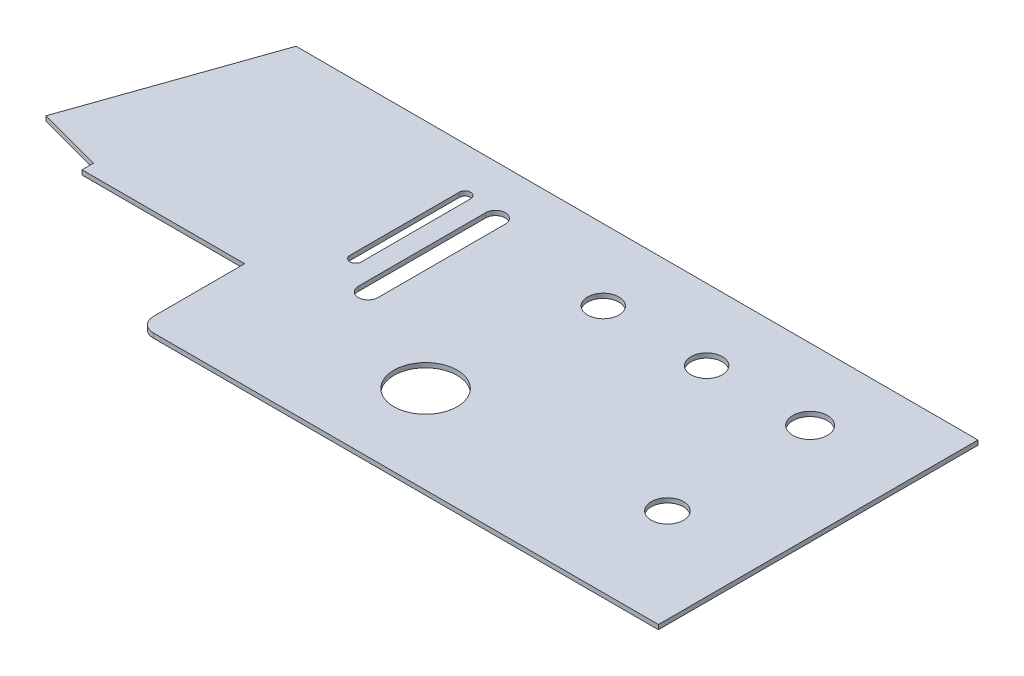
SolidWorks part; units mm, degrees
ref_plane "Front Plane" through (0, 0, 0) normal (0, 0, 1) x (1, 0, 0)
ref_plane "Top Plane" through (0, 0, 0) normal (0, 1, 0) x (1, 0, 0)
ref_plane "Right Plane" through (0, 0, 0) normal (1, 0, 0) x (0, 0, -1)
sketch "Sketch1" plane through (0, 0, 0) normal (0, 1, 0) x (1, 0, 0)
  line L0 (-101.3722, -12.5155) -> (-44.3722, -12.5155) construction
  line L1 (-44.3722, -53.5155) -> (137.6278, -53.5155) construction
  line L2 (-101.3722, -12.5155) -> (-101.3722, 58.4845) construction
  line L3 (-101.3722, 58.4845) -> (137.6278, 58.4845) construction
  line L4 (137.6278, -53.5155) -> (137.6278, 58.4845) construction
  line L5 (-44.3722, -12.5155) -> (-44.3722, -53.5155) construction
  line L6 (-26.4722, 42.7845) -> (-26.4722, 4.4845) construction
  line L7 (-23.4722, 42.7845) -> (-23.4722, 4.4845) construction
  line L8 (-29.4722, 42.7845) -> (-29.4722, 4.4845) construction
  line L9 (-14.1722, 41.1845) -> (-14.1722, -3.4155) construction
  line L10 (-9.5722, 41.1845) -> (-9.5722, -3.4155) construction
  line L11 (-18.7722, 41.1845) -> (-18.7722, -3.4155) construction
  line L12 (-26.4722, 45.7845) -> (-43.4588, 45.7845) construction
  line L13 (-26.4722, 1.4845) -> (-43.4588, 1.4845) construction
  line L14 (-14.1722, -8.0155) -> (-3.3024, -8.0155) construction
  line L15 (-14.1722, 45.7845) -> (0, 45.7845) construction
  line L16 (31.286, 33.4845) -> (122.5273, 33.4845) construction
  arc A0 (-23.4722, 42.7845) -> (-29.4722, 42.7845) centre (-26.4722, 42.7845) ccw construction
  arc A1 (-29.4722, 4.4845) -> (-23.4722, 4.4845) centre (-26.4722, 4.4845) ccw construction
  arc A2 (-9.5722, 41.1845) -> (-18.7722, 41.1845) centre (-14.1722, 41.1845) ccw construction
  arc A3 (-18.7722, -3.4155) -> (-9.5722, -3.4155) centre (-14.1722, -3.4155) ccw construction
  circle A7 centre (25.1778, -22.6655) radius 11.15 construction
  circle A8 centre (104.7278, -17.4655) radius 5.95 construction
  circle A9 centre (31.286, 33.4845) radius 6.25 construction
  circle A10 centre (67.536, 33.4845) radius 6.25 construction
  circle A11 centre (103.786, 33.4845) radius 6.25 construction
  point P0 (0, 0)
  point P10 (-26.4722, 23.6345)
  point P15 (-14.1722, 18.8845)
  point P24 (0, 0)
  dimension "D5" = 3
  dimension "D6" = 4.6
  dimension "D7" = 44.3
  dimension "D9" = 12.5
  dimension "D10" = 22.3
  dimension "D11" = 11.9
  dimension "D14" = 149.1
  dimension "D16" = 12.7
  dimension "D19" = 81.15
  dimension "D1" = 239
  dimension "D2" = 182
  dimension "D3" = 74.9
  dimension "D4" = 87.2
  dimension "D8" = 53.8
  dimension "D12" = 112
  dimension "D13" = 69.55
  dimension "D15" = 12.7
  dimension "D17" = 25
  dimension "D20" = 75.95
  dimension "D21" = 71
  dimension "D22" = 41
  dimension "D18" = 3
sketch "Sketch2" plane through (0, 0, 0) normal (0, 1, 0) x (1, 0, 0)
  line L1 (-101.3722, 58.4845) -> (137.6278, 58.4845)
  line L3 (-39.3722, -53.5155) -> (137.6278, -53.5155)
  line L4 (137.6278, 58.4845) -> (137.6278, -53.5155)
  line L5 (-44.3722, -16.5155) -> (-44.3722, -48.5155)
  line L6 (-26.4722, 4.4845) -> (-26.4722, 42.7845) construction
  line L7 (-28.4722, 4.4845) -> (-28.4722, 42.7845)
  line L8 (-24.4722, 4.4845) -> (-24.4722, 42.7845)
  line L9 (-14.1722, 41.1845) -> (-14.1722, -3.4155) construction
  line L10 (-10.7222, 41.1845) -> (-10.7222, -3.4155)
  line L11 (-17.6222, 41.1845) -> (-17.6222, -3.4155)
  line L12 (-101.3722, -12.5155) -> (-101.3722, -16.5155)
  line L13 (-101.3722, -16.5155) -> (-44.8722, -16.5155)
  line L15 (-101.3722, -12.5155) -> (-124.0715, -6.4333)
  line L16 (-124.0715, -6.4333) -> (-101.3722, 58.4845)
  line L17 (-44.8722, -16.5155) -> (-44.3722, -16.5155)
  arc A0 (-28.4722, 4.4845) -> (-24.4722, 4.4845) centre (-26.4722, 4.4845) ccw
  arc A1 (-24.4722, 42.7845) -> (-28.4722, 42.7845) centre (-26.4722, 42.7845) ccw
  arc A2 (-10.7222, 41.1845) -> (-17.6222, 41.1845) centre (-14.1722, 41.1845) ccw
  arc A3 (-17.6222, -3.4155) -> (-10.7222, -3.4155) centre (-14.1722, -3.4155) ccw
  circle A4 centre (31.286, 33.4845) radius 5.5
  circle A5 centre (67.536, 33.4845) radius 5.5
  circle A6 centre (103.786, 33.4845) radius 6.05
  circle A7 centre (25.1778, -22.6655) radius 11.1
  circle A8 centre (104.7278, -17.4655) radius 5.65
  arc A11 (-44.3722, -48.5155) -> (-39.3722, -53.5155) centre (-39.3722, -48.5155) ccw
  point P15 (-26.4722, 23.6345)
  point P24 (-14.1722, 18.8845)
  point P50 (-44.3722, -53.5155)
  dimension "D1" = 2
  dimension "D2" = 3.45
  dimension "D3" = 11
  dimension "D4" = 11
  dimension "D5" = 12.1
  dimension "D6" = 22.2
  dimension "D7" = 11.3
  dimension "D8" = 5
  dimension "D9" = 4
  dimension "D12" = 23.5
extrude "Boss-Extrude1" add sketch "Sketch2" along normal blind 1.6
